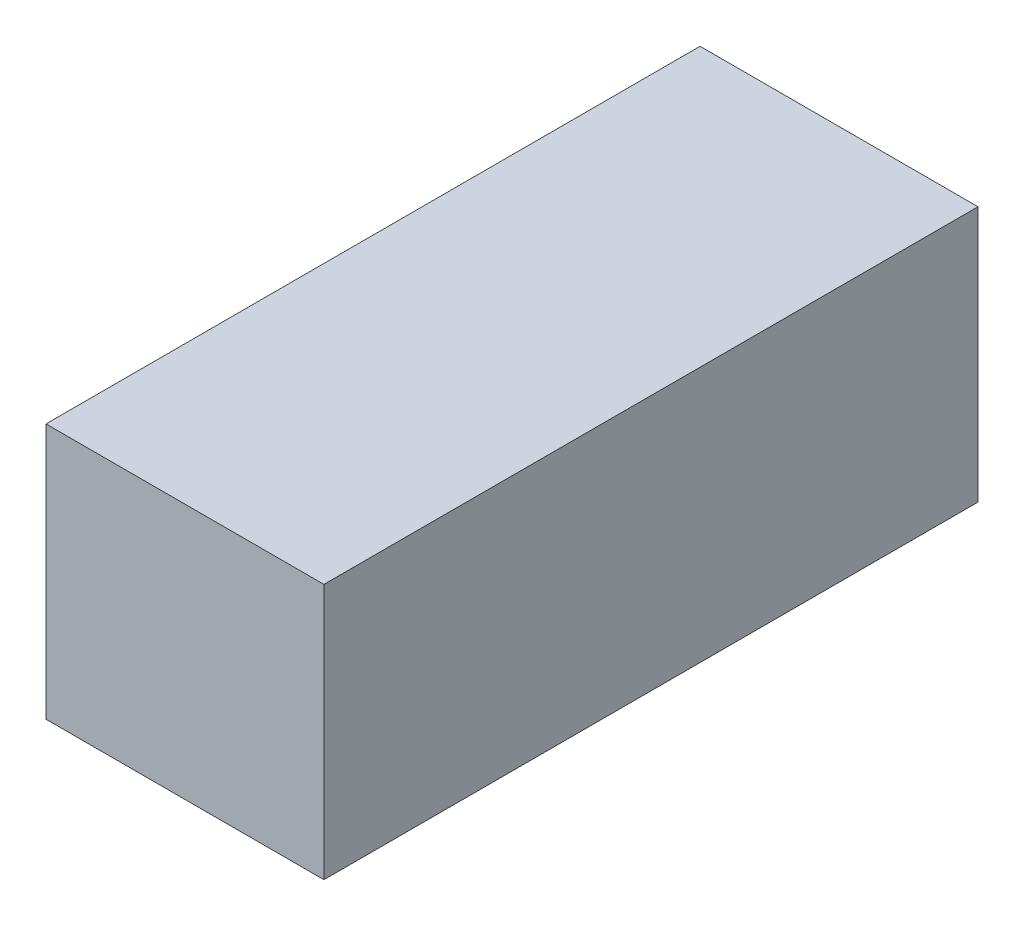
SolidWorks part; units mm, degrees
material "Magnetometer"
ref_plane "Piano frontale" through (0, 0, 0) normal (0, 0, 1) x (1, 0, 0)
ref_plane "Piano superiore" through (0, 0, 0) normal (0, 1, 0) x (1, 0, 0)
ref_plane "Piano destro" through (0, 0, 0) normal (1, 0, 0) x (0, 0, -1)
sketch "Schizzo1" plane through (0, 0, 0) normal (0, 0, 1) x (1, 0, 0)
  line L1 (-17.55, -16.15) -> (17.55, -16.15)
  line L2 (-17.55, -16.15) -> (-17.55, 16.15)
  line L3 (-17.55, 16.15) -> (17.55, 16.15)
  line L4 (17.55, -16.15) -> (17.55, 16.15)
  line L5 (-17.55, -16.15) -> (17.55, 16.15) construction
  line L6 (-17.55, 16.15) -> (17.55, -16.15) construction
  point P0 (0, 0)
  dimension "D1" = 35.1
  dimension "D2" = 32.3
extrude "Estrusione-Estrusione1" add sketch "Schizzo1" along normal blind 41.3 and the other way blind 41.3
